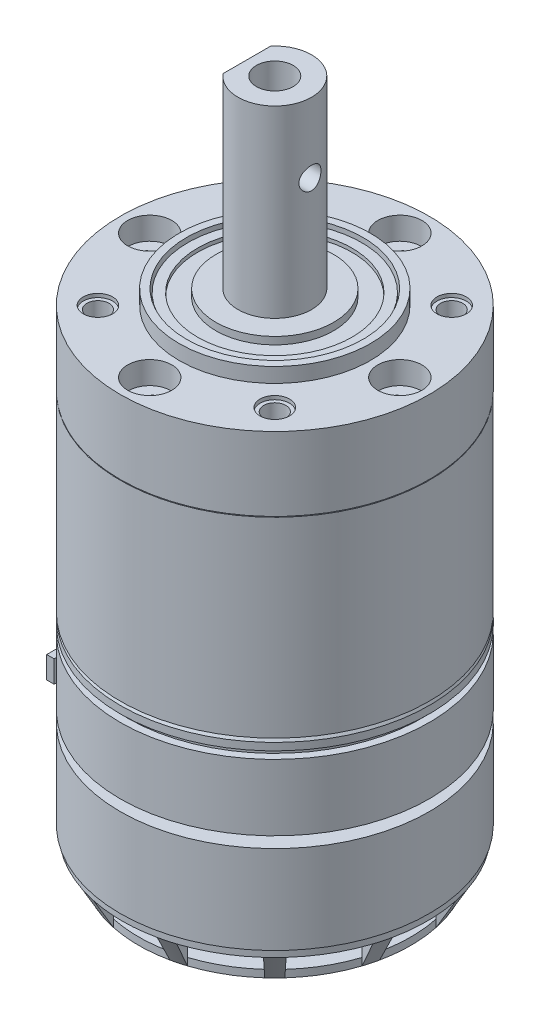
SolidWorks part; units mm, degrees
note: The reader was unsure of these and kept them because the rebuilt part matched: shared geometry of "草图27<3>".
material "钛 Ti-8Al-1Mo-1V"
ref_plane "前视基准面" through (0, 0, 0) normal (0, 0, 1) x (1, 0, 0)
ref_plane "上视基准面" through (0, 0, 0) normal (0, 1, 0) x (1, 0, 0)
ref_plane "右视基准面" through (0, 0, 0) normal (1, 0, 0) x (0, 0, -1)
sketch "草图1" plane through (0, 0, 0) normal (0, 1, 0) x (1, 0, 0)
  circle A0 centre (0, 0) radius 21
  dimension "D1" = 42
extrude "凸台-拉伸1" add sketch "草图1" along normal blind 12
sketch "草图2" plane through (0, 12, 0) normal (0, 1, 0) x (1, 0, 0)
  circle A0 centre (0, 0) radius 10
  dimension "D1" = 20
extrude "凸台-拉伸2" add sketch "草图2" along normal blind 1.5
sketch "草图3" plane through (0, 13.5, 0) normal (0, 1, 0) x (1, 0, 0)
  circle A0 centre (0, 0) radius 21
  dimension "D1" = 42
extrude "凸台-拉伸3" add sketch "草图3" along normal blind 9
sketch "草图4" plane through (0, 22.5, 0) normal (0, 1, 0) x (1, 0, 0)
  circle A0 centre (0, 0) radius 20
  dimension "D1" = 40
extrude "凸台-拉伸4" add sketch "草图4" along normal blind 1
sketch "草图5" plane through (0, 23.5, 0) normal (0, 1, 0) x (1, 0, 0)
  circle A0 centre (0, 0) radius 21
  dimension "D1" = 42
extrude "凸台-拉伸5" add sketch "草图5" along normal blind 1
sketch "草图6" plane through (0, 0, 0) normal (1, 0, 0) x (0, 0, -1)
  line L0 (-21, 24.5) -> (-20.7113, 25)
  line L1 (-20.7113, 25) -> (0, 25)
  line L2 (0, 25) -> (0, 24.5)
  line L4 (21, 24.5) -> (-21, 24.5) construction
  line L5 (0, 24.5) -> (-21, 24.5)
  dimension "D1" = 0.5
  dimension "D2" = 60
revolve "旋转1" add sketch "草图6" angle 360 about L2
sketch "草图7" plane through (0, 25, 0) normal (0, 1, 0) x (1, 0, 0)
  circle A0 centre (0, 0) radius 21
  dimension "D1" = 42
extrude "凸台-拉伸6" add sketch "草图7" along normal blind 26
sketch "草图8" plane through (0, 51, 0) normal (0, 1, 0) x (1, 0, 0)
  circle A0 centre (0, 0) radius 20.5
  dimension "D1" = 41
extrude "凸台-拉伸7" add sketch "草图8" along normal blind 0.1
sketch "草图9" plane through (0, 51.1, 0) normal (0, 1, 0) x (1, 0, 0)
  circle A0 centre (0, 0) radius 21
  dimension "D1" = 42
extrude "凸台-拉伸8" add sketch "草图9" along normal blind 10
sketch "草图11" plane through (0, 61.1, 0) normal (0, 1, 0) x (1, 0, 0)
  circle A0 centre (0, 0) radius 13
  dimension "D1" = 26
extrude "凸台-拉伸9" add sketch "草图11" along normal blind 2
sketch "草图12" plane through (0, 63.1, 0) normal (0, 1, 0) x (1, 0, 0)
  circle A0 centre (0, 0) radius 8
  circle A1 centre (0, 0) radius 12
  dimension "D1" = 16
  dimension "D2" = 24
extrude "切除-拉伸1" cut sketch "草图12" against normal blind 1
sketch "草图13" plane through (0, 62.1, 0) normal (0, 1, 0) x (1, 0, 0)
  circle A0 centre (0, 0) radius 12
  circle A1 centre (0, 0) radius 10.5
  dimension "D1" = 21
extrude "凸台-拉伸10" add sketch "草图13" along normal blind 0.5
sketch "草图14" plane through (0, 62.6, 0) normal (0, 1, 0) x (1, 0, 0)
  circle A0 centre (0, 0) radius 12
  circle A1 centre (0, 0) radius 11.8
  dimension "D1" = 0.2
extrude "切除-拉伸2" cut sketch "草图14" against normal blind 2
sketch "草图15" plane through (0, 63.1, 0) normal (0, 1, 0) x (1, 0, 0)
  circle A0 centre (0, 0) radius 5
  dimension "D1" = 10
extrude "凸台-拉伸11" add sketch "草图15" along normal blind 5
sketch "草图16" plane through (0, 68.1, 0) normal (0, 1, 0) x (1, 0, 0)
  line L0 (0, 7.3912) -> (0, -6.9977) construction
  line L1 (5, 0) -> (5, 7.3912) construction
  line L2 (-3.8, 3.2496) -> (-3.8, -3.2496)
  arc A0 (-3.8, -3.2496) -> (-3.8, 3.2496) centre (0, 0) ccw
  dimension "D1" = 8.8
extrude "凸台-拉伸12" add sketch "草图16" along normal blind 20
sketch "草图17" plane through (-3.8, 0, 0) normal (-1, 0, 0) x (0, 0, 1)
  line L0 (-3.2496, 88.1) -> (3.2496, 88.1) construction
  line L1 (-3.2496, 80.1) -> (3.2496, 80.1) construction
  line L2 (-3.2496, 88.1) -> (-3.2496, 68.1) construction
  line L3 (3.2496, 88.1) -> (3.2496, 68.1) construction
  line L4 (0, 88.1) -> (0, 68.1) construction
  line L5 (-3.2496, 68.1) -> (3.2496, 68.1) construction
  circle A0 centre (0, 78.6) radius 1.5
  dimension "D2" = 3
  dimension "D1" = 8
extrude "切除-拉伸3" cut sketch "草图17" against normal blind 9
sketch "草图18" plane through (0, 0, 0) normal (0, -1, 0) x (1, 0, 0)
  circle A0 centre (0, 0) radius 20.75
  circle A1 centre (0, 0) radius 18.5
  dimension "D1" = 41.5
  dimension "D2" = 37
extrude "凸台-拉伸16" add sketch "草图18" along normal blind 1
sketch "草图23" plane through (0, 0, 0) normal (1, 0, 0) x (0, 0, -1)
  line L0 (0, 0) -> (0, -4.9657)
  line L1 (0, 0) -> (-18.5, 0)
  line L2 (-18.5, -1) -> (-18.5, -5)
  line L3 (-18.5, -5) -> (-18.5, -1)
  line L4 (-20.75, -1) -> (20.75, -1) construction
  line L5 (-18.5, -1) -> (-20.75, -1)
  line L6 (-18.5, -5) -> (-20.75, -1)
  dimension "D1" = 18.5
  dimension "D2" = 4
revolve "旋转2" add sketch "草图23" angle 360 about L0
ref_plane "基准面1" through (0, -4, 0) normal (0, -1, 0) x (-1, 0, 0)
sketch "草图24" plane through (0, -4, 0) normal (0, -1, 0) x (-1, 0, 0)
  circle A0 centre (0, 0) radius 18.5
extrude "凸台-拉伸17" add sketch "草图24" along normal blind 1
sketch "草图25" plane through (0, -5, 0) normal (0, -1, 0) x (1, 0, 0)
  line L0 (0, 22.5177) -> (0, -22.7841) construction
  line L1 (-3.8464, -18.0957) -> (-4.3142, -20.2966)
  line L2 (3.8464, -18.0957) -> (4.3142, -20.2966)
  line L3 (-12.3789, -13.7482) -> (-13.8845, -15.4203)
  line L4 (-5.7168, -17.5945) -> (-6.4121, -19.7344)
  line L5 (-17.5945, -5.7168) -> (-19.7344, -6.4121)
  line L6 (-13.7482, -12.3789) -> (-15.4203, -13.8845)
  line L7 (-18.0957, 3.8464) -> (-20.2966, 4.3142)
  line L8 (-18.0957, -3.8464) -> (-20.2966, -4.3142)
  line L9 (-13.7482, 12.3789) -> (-15.4203, 13.8845)
  line L10 (-17.5945, 5.7168) -> (-19.7344, 6.4121)
  line L11 (-5.7168, 17.5945) -> (-6.4121, 19.7344)
  line L12 (-12.3789, 13.7482) -> (-13.8845, 15.4203)
  line L13 (3.8464, 18.0957) -> (4.3142, 20.2966)
  line L14 (-3.8464, 18.0957) -> (-4.3142, 20.2966)
  line L15 (12.3789, 13.7482) -> (13.8845, 15.4203)
  line L16 (5.7168, 17.5945) -> (6.4121, 19.7344)
  line L17 (17.5945, 5.7168) -> (19.7344, 6.4121)
  line L18 (13.7482, 12.3789) -> (15.4203, 13.8845)
  line L19 (18.0957, -3.8464) -> (20.2966, -4.3142)
  line L20 (18.0957, 3.8464) -> (20.2966, 4.3142)
  line L21 (13.7482, -12.3789) -> (15.4203, -13.8845)
  line L22 (17.5945, -5.7168) -> (19.7344, -6.4121)
  line L23 (5.7168, -17.5945) -> (6.4121, -19.7344)
  line L24 (12.3789, -13.7482) -> (13.8845, -15.4203)
  circle A0 centre (0, 0) radius 20.75
  circle A1 centre (0, 0) radius 18.5
  point P56 (0, 0)
  circle M1 centre (0, 0) radius 18.5
  dimension "D1" = 12
  dimension "D2" = 12
extrude "切除-拉伸5" cut sketch "草图25" against normal blind 4 contours L11 A0 L12 M1 | A0 L0 L13 M1 | L0 A0 L14 A1 | L15 A0 L16 M1 | L17 A0 L18 M1 | L19 A0 L20 M1 | L21 A0 L22 M1 | L23 A0 L24 M1 | A1 L0 A0 L2 | L0 L1 A0 M1 | L3 A0 L4 M1 | L5 A0 L6 M1 | L7 A0 L8 M1 | L9 A0 L10 M1
sketch "草图26" plane through (0, 0, 0) normal (1, 0, 0) x (0, 0, -1)
  line L0 (21, 19.5) -> (-21, 19.5) construction
  line L1 (21, 13.5) -> (21, 22.5) construction
  line L2 (-21, 22.5) -> (-21, 13.5) construction
  line L3 (21, 22.5) -> (-21, 22.5) construction
  line L4 (21, 16.5) -> (-21, 16.5) construction
  line L5 (-5, 19.5) -> (-5, 16.5)
  line L6 (-5, 19.5) -> (-15, 19.5)
  line L7 (-15, 16.5) -> (-15, 19.5)
  line L8 (-5, 16.5) -> (-15, 16.5)
  dimension "D1" = 3
  dimension "D2" = 3
  dimension "D3" = 6
  dimension "D4" = 10
extrude "切除-拉伸6" cut sketch "草图26" against normal blind 21
sketch "草图27" plane through (0, 61.1, 0) normal (0, 1, 0) x (1, 0, 0)
  line L0 (0, 17) -> (17, 0) construction
  line L1 (0, 0) -> (12.0208, 12.0208) construction
  circle A0 centre (0, 0) radius 17 construction
  circle A1 centre (0, 17) radius 3
  circle A2 centre (17, 0) radius 3
  circle A3 centre (0, -17) radius 3
  circle A4 centre (-17, 0) radius 3
  circle A5 centre (12.0208, 12.0208) radius 2
  circle A6 centre (12.0208, -12.0208) radius 2
  circle A7 centre (-12.0208, -12.0208) radius 2
  circle A8 centre (-12.0208, 12.0208) radius 2
  point P14 (0, 0)
  point P23 (0, 0)
  dimension "D1" = 34
  dimension "D2" = 6
  dimension "D3" = 4
  dimension "D4" = 4
  dimension "D5" = 4
extrude "切除-拉伸7" cut sketch "草图27" against normal blind 5 contours A1 | A4 | A3 | A2
extrude "切除-拉伸8" cut sketch "草图27<3>" against normal blind 0.5 contours A8 | A6 | A7 | A5
sketch "草图27<3>" plane through (0, 61.1, 0) normal (0, 1, 0) x (1, 0, 0) same geometry as "草图27"
sketch "草图28" plane through (0, 60.6, 0) normal (0, 1, 0) x (1, 0, 0)
  circle A0 centre (-12.0208, 12.0208) radius 1.5
  circle A1 centre (12.0208, 12.0208) radius 1.5
  circle A2 centre (12.0208, -12.0208) radius 1.5
  circle A3 centre (-12.0208, -12.0208) radius 1.5
  point P12 (0, 0)
  dimension "D1" = 3
  dimension "D2" = 4
extrude "切除-拉伸9" cut sketch "草图28" against normal blind 4
sketch "草图29" plane through (0, 56.1, 0) normal (0, 1, 0) x (1, 0, 0)
  line L0 (17, -1.4136) -> (18.2242, -0.7068)
  line L1 (1.4136, 17) -> (0.7068, 18.2242)
  line L2 (0.7068, 18.2242) -> (-0.7068, 18.2242)
  line L3 (-0.7068, 18.2242) -> (-1.4136, 17)
  line L4 (-1.4136, 17) -> (-0.7068, 15.7758)
  line L5 (-0.7068, 15.7758) -> (0.7068, 15.7758)
  line L6 (0.7068, 15.7758) -> (1.4136, 17)
  line L7 (18.2242, -0.7068) -> (18.2242, 0.7068)
  line L8 (18.2242, 0.7068) -> (17, 1.4136)
  line L9 (17, 1.4136) -> (15.7758, 0.7068)
  line L10 (15.7758, 0.7068) -> (15.7758, -0.7068)
  line L11 (15.7758, -0.7068) -> (17, -1.4136)
  line L12 (-1.4136, -17) -> (-0.7068, -18.2242)
  line L13 (-0.7068, -18.2242) -> (0.7068, -18.2242)
  line L14 (0.7068, -18.2242) -> (1.4136, -17)
  line L15 (1.4136, -17) -> (0.7068, -15.7758)
  line L16 (0.7068, -15.7758) -> (-0.7068, -15.7758)
  line L17 (-0.7068, -15.7758) -> (-1.4136, -17)
  line L18 (-17, 1.4136) -> (-18.2242, 0.7068)
  line L19 (-18.2242, 0.7068) -> (-18.2242, -0.7068)
  line L20 (-18.2242, -0.7068) -> (-17, -1.4136)
  line L21 (-17, -1.4136) -> (-15.7758, -0.7068)
  line L22 (-15.7758, -0.7068) -> (-15.7758, 0.7068)
  line L23 (-15.7758, 0.7068) -> (-17, 1.4136)
  circle A0 centre (0, 17) radius 2.9
  circle A1 centre (0, 17) radius 1.2242 construction
  circle A2 centre (17, 0) radius 2.9
  circle A3 centre (0, -17) radius 2.9
  circle A4 centre (-17, 0) radius 2.9
  point P37 (0, 0)
  dimension "D1" = 5.8
  dimension "D2" = 4
extrude "凸台-拉伸18" add sketch "草图29" along normal blind 2
sketch "草图30" plane through (0, -5, 0) normal (0, -1, 0) x (1, 0, 0)
  circle A0 centre (0, 0) radius 3.4
  dimension "D1" = 6.8
extrude "凸台-拉伸19" add sketch "草图30" along normal blind 5 and the other way up to surface other way up to face at (0, 0, -18.5)
sketch "草图31" plane through (0, -5, 0) normal (0, -1, 0) x (1, 0, 0)
  circle A0 centre (0, 0) radius 5.5 construction
  circle A1 centre (5.5, 0) radius 1.5
  circle A2 centre (-5.5, 0) radius 1.5
  point P9 (0, 0)
  dimension "D1" = 11
  dimension "D2" = 3
  dimension "D3" = 2
extrude "切除-拉伸10" cut sketch "草图31" against normal blind 10
sketch "草图32" plane through (0, 88.1, 0) normal (0, 1, 0) x (1, 0, 0)
  circle A0 centre (0, 0) radius 2.5
extrude "切除-拉伸11" cut sketch "草图32" against normal blind 50
ref_plane "基准面2" through (-16, 0, 0) normal (-1, 0, 0) x (0, 0, 1)
sketch "草图33" plane through (-16, 0, 0) normal (-1, 0, 0) x (0, 0, 1)
  line L0 (15, 16.5) -> (5, 16.5) construction
  line L1 (15, 19.5) -> (7.8365, 19.5)
  line L2 (15, 19.5) -> (15, 16.5)
  line L3 (15, 16.5) -> (7.8365, 16.5)
  line L4 (7.8365, 19.5) -> (7.8365, 16.5)
  line L5 (7.8365, 19.5) -> (15, 16.5) construction
  line L6 (15, 19.5) -> (7.8365, 16.5) construction
  line L7 (11.4183, 19.5) -> (11.4183, 16.5) construction
  line L8 (14.4854, 17.3096) -> (14.4854, 17.7844)
  line L9 (9.6936, 18.15) -> (13.1429, 18.15)
  line L10 (9.6936, 18.15) -> (9.6936, 17.5993)
  line L11 (9.6936, 17.5993) -> (13.1429, 17.5993)
  line L12 (13.1429, 18.15) -> (13.1429, 17.5993)
  line L13 (9.6936, 18.15) -> (13.1429, 17.5993) construction
  line L14 (9.6936, 17.5993) -> (13.1429, 18.15) construction
  line L15 (8.6981, 17.3096) -> (14.1385, 17.3096)
  line L16 (8.3512, 17.3096) -> (8.3512, 16.5599)
  line L17 (8.3512, 16.5599) -> (14.4854, 16.5599)
  line L18 (14.4854, 17.3096) -> (14.4854, 16.5599)
  line L19 (8.3512, 17.3096) -> (14.4854, 16.5599) construction
  line L20 (8.3512, 16.5599) -> (14.4854, 17.3096) construction
  line L21 (14.4854, 17.7844) -> (14.1385, 17.7844)
  line L22 (14.1385, 17.7844) -> (14.1385, 17.3096)
  line L23 (8.6981, 17.7844) -> (8.6981, 17.3096)
  line L24 (8.3512, 17.7844) -> (8.6981, 17.7844)
  line L25 (8.3512, 17.3096) -> (8.3512, 17.7844)
  line L26 (14.232, 18.262) -> (12.0439, 18.262)
  line L27 (8.6045, 19.1784) -> (10.7926, 19.1784)
  line L28 (8.6045, 19.1784) -> (8.6045, 18.262)
  line L29 (8.6045, 18.262) -> (10.7926, 18.262)
  line L30 (10.7926, 19.1784) -> (10.7926, 18.262)
  line L31 (8.6045, 19.1784) -> (10.7926, 18.262) construction
  line L32 (8.6045, 18.262) -> (10.7926, 19.1784) construction
  line L33 (12.0439, 19.1784) -> (12.0439, 18.262)
  line L34 (14.232, 19.1784) -> (12.0439, 19.1784)
  line L35 (14.232, 19.1784) -> (14.232, 18.262)
  line L36 (14.232, 18.262) -> (12.0439, 19.1784) construction
  line L37 (14.232, 19.1784) -> (12.0439, 18.262) construction
  point P9 (11.4183, 17.8746)
  point P14 (11.4183, 16.9347)
  point P25 (9.6985, 18.7202)
  point P34 (13.138, 18.7202)
extrude "凸台-拉伸20" add sketch "草图33" against normal blind 1 contours L1 L4 L3 L2 L27 L30 L29 L28 L9 L12 L11 L10 L16 L25 L24 L23 L15 L22 L21 L8 L18 L17 L34 L35 L26 L33
sketch "草图36" plane through (0, 0, 0) normal (-1, 0, 0) x (0, 0, 1)
  line L1 (-10.905, 20) -> (3.095, 20)
  line L2 (-10.905, 20) -> (-10.905, 16)
  line L3 (-10.905, 16) -> (3.095, 16)
  line L4 (3.095, 20) -> (3.095, 16)
  circle A0 centre (0.4959, 18) radius 1.5
  circle A1 centre (-4.0041, 18) radius 1.5
  circle A2 centre (-8.5041, 18) radius 1.5
  dimension "D3" = 3
  dimension "D1" = 14
  dimension "D2" = 4
extrude "凸台-拉伸21" add sketch "草图36" along normal offset from surface (22.2861 mm away) 1.5
sketch "草图37" plane through (0, 0, 0) normal (1, 0, 0) x (0, 0, -1)
  circle A0 centre (8.5041, 18) radius 1
  circle A1 centre (4.0041, 18) radius 1
  circle A2 centre (-0.4959, 18) radius 1
  dimension "D1" = 3
extrude "凸台-拉伸22" add sketch "草图37" against normal offset from surface (22.038 mm away) 1.5
